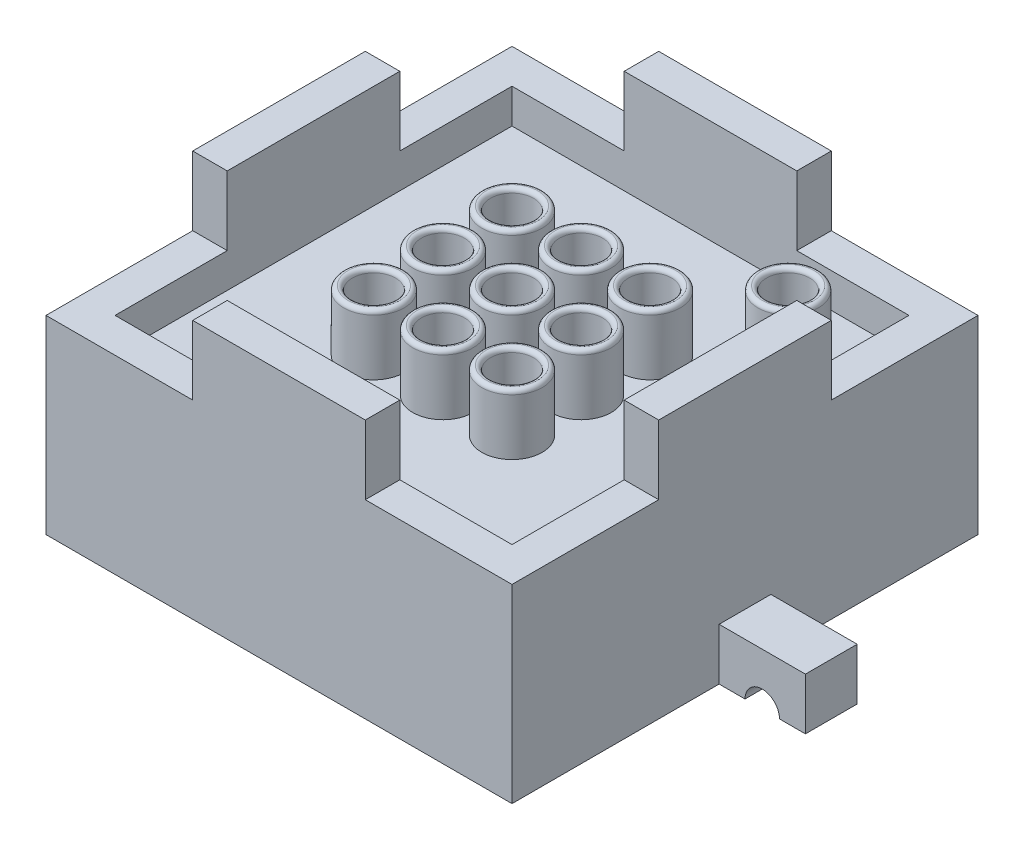
SolidWorks part; units mm, degrees
ref_plane "Front Plane" through (0, 0, 0) normal (0, 0, 1) x (1, 0, 0)
ref_plane "Top Plane" through (0, 0, 0) normal (0, 1, 0) x (1, 0, 0)
ref_plane "Right Plane" through (0, 0, 0) normal (1, 0, 0) x (0, 0, -1)
sketch "Sketch1" plane through (0, 0, 0) normal (0, 1, 0) x (1, 0, 0)
  line L0 (-13.5, 13.5) -> (13.5, 13.5)
  line L1 (-11.5, -11.5) -> (11.5, -11.5)
  line L2 (-11.5, -11.5) -> (-11.5, 11.5)
  line L3 (-11.5, 11.5) -> (11.5, 11.5)
  line L4 (11.5, -11.5) -> (11.5, 11.5)
  line L5 (-11.5, -11.5) -> (11.5, 11.5) construction
  line L6 (-11.5, 11.5) -> (11.5, -11.5) construction
  line L7 (13.5, -13.5) -> (13.5, 13.5)
  line L8 (-13.5, -13.5) -> (13.5, -13.5)
  line L9 (-13.5, -13.5) -> (-13.5, 13.5)
  point P0 (0, 0)
  dimension "D1" = 23
  dimension "D2" = 2
extrude "Boss-Extrude1" add sketch "Sketch1" along normal blind 2
sketch "Sketch2" plane through (0, 0, 0) normal (0, -1, 0) x (1, 0, 0)
  line L1 (-13.5, 13.5) -> (13.5, 13.5)
  line L2 (-13.5, 13.5) -> (-13.5, -13.5)
  line L3 (-13.5, -13.5) -> (13.5, -13.5)
  line L4 (13.5, 13.5) -> (13.5, -13.5)
  line L5 (-13.5, 13.5) -> (13.5, -13.5) construction
  line L6 (-13.5, -13.5) -> (13.5, 13.5) construction
  point P0 (0, 0)
extrude "Boss-Extrude2" add sketch "Sketch2" along normal blind 2
sketch "Sketch3" plane through (0, -2, 0) normal (0, -1, 0) x (1, 0, 0)
  line L0 (-11.5, 11.5) -> (11.5, 11.5)
  line L1 (-13.5, -13.5) -> (13.5, -13.5)
  line L2 (-13.5, -13.5) -> (-13.5, 13.5)
  line L3 (-13.5, 13.5) -> (13.5, 13.5)
  line L4 (13.5, -13.5) -> (13.5, 13.5)
  line L5 (-13.5, -13.5) -> (13.5, 13.5) construction
  line L6 (-13.5, 13.5) -> (13.5, -13.5) construction
  line L7 (11.5, -11.5) -> (11.5, 11.5)
  line L8 (-11.5, -11.5) -> (11.5, -11.5)
  line L9 (-11.5, -11.5) -> (-11.5, 11.5)
  point P0 (0, 0)
  dimension "D1" = 2
extrude "Boss-Extrude3" add sketch "Sketch3" along normal blind 5
sketch "Sketch6" plane through (0, 0, 0) normal (0, 1, 0) x (1, 0, 0)
  line L0 (11.5, -11.5) -> (11.5, 11.5) construction
  line L1 (11.5, 11.5) -> (-11.5, 11.5) construction
  circle A0 centre (8, 8) radius 1.75
  dimension "D2" = 3.5
  dimension "D1" = 3.5
  dimension "D3" = 3.5
extrude "Boss-Extrude5" add sketch "Sketch6" along normal blind 3.5
sketch "Sketch7" plane through (0, 3.5, 0) normal (0, 1, 0) x (1, 0, 0)
  circle A0 centre (8, 8) radius 1.25
  circle A1 centre (8, 8) radius 1.75 construction
  dimension "D1" = 0.5
extrude "Cut-Extrude2" cut sketch "Sketch7" against normal up to next
fillet "Fillet1" radius 0.25 2 edges at (8, 3.5, -6.25) (8, 3.5, -6.75)
pattern_linear "LPattern3" count 5 spacing 4 along (0, 0, 1) count 5 spacing 4 along (-1, 0, 0) skipping (0, 1), (0, 2), (0, 3), (0, 4), (1, 0), (1, 4), (2, 0), (2, 4), (3, 0), (3, 4), (4, 0), (4, 1), (4, 2), (4, 3), (4, 4) of "Boss-Extrude5", "Cut-Extrude2", "Fillet1"
sketch "Sketch11" plane through (0, -2, 0) normal (0, -1, 0) x (1, 0, 0)
  line L0 (11.5, 11.5) -> (-11.5, 11.5) construction
  line L1 (-11.5, 11.5) -> (-11.5, -11.5) construction
  circle A0 centre (-9.9, 9.9) radius 0.75
  dimension "D1" = 1.5
  dimension "D3" = 1.6
  dimension "D2" = 1.6
extrude "Boss-Extrude8" add sketch "Sketch11" along normal up to surface (5 mm away) up to face at (0, -7, 0)
pattern_linear "LPattern2" count 6 spacing 4 along (1, 0, 0) count 6 spacing 4 along (0, 0, -1) of "Boss-Extrude8"
sketch "Sketch8" plane through (0, -7, 0) normal (0, -1, 0) x (1, 0, 0)
  line L1 (-13.5, -13.5) -> (13.5, -13.5)
  line L2 (-13.5, -13.5) -> (-13.5, 13.5)
  line L3 (-13.5, 13.5) -> (13.5, 13.5)
  line L4 (13.5, -13.5) -> (13.5, 13.5)
  line L5 (-13.5, -13.5) -> (13.5, 13.5) construction
  line L6 (-13.5, 13.5) -> (13.5, -13.5) construction
  point P0 (0, 0)
extrude "Boss-Extrude6" add sketch "Sketch8" along normal blind 2
sketch "Sketch9" plane through (0, -9, 0) normal (0, -1, 0) x (1, 0, 0)
  circle A0 centre (0, 0) radius 4.25
  dimension "D1" = 8.5
extrude "Cut-Extrude3" cut sketch "Sketch9" against normal blind 7
sketch "Sketch10" plane through (0, 2, 0) normal (0, 1, 0) x (1, 0, 0)
  line L0 (-13.5, 0) -> (-11.5, 0) construction
  line L1 (-13.5, 13.5) -> (-13.5, -13.5) construction
  line L2 (-11.5, 11.5) -> (-11.5, -11.5) construction
  line L4 (-11.5, 5) -> (-13.5, 5)
  line L5 (-11.5, 5) -> (-11.5, -5)
  line L6 (-11.5, -5) -> (-13.5, -5)
  line L7 (-13.5, 5) -> (-13.5, -5)
  line L8 (-11.5, 5) -> (-13.5, -5) construction
  line L9 (-11.5, -5) -> (-13.5, 5) construction
  point P6 (-12.5, 0)
  dimension "D1" = 10
extrude "Boss-Extrude7" add sketch "Sketch10" along normal blind 4
pattern_circular "CirPattern2" count 4 over 360 about axis through (0, -7.001, 0) along (0, 1, 0) of "Boss-Extrude7"
sketch "Sketch12" plane through (-13.5, 0, 0) normal (-1, 0, 0) x (0, 0, 1)
  line L0 (13.5, -9) -> (-13.5, -9) construction
  line L1 (1.5, -6) -> (-1.5, -6)
  line L2 (1.5, -6) -> (1.5, -9)
  line L3 (1.5, -9) -> (-1.5, -9)
  line L4 (-1.5, -6) -> (-1.5, -9)
  line L5 (1.5, -6) -> (-1.5, -9) construction
  line L6 (1.5, -9) -> (-1.5, -6) construction
  line L7 (0, 0) -> (0, -9) construction
  point P0 (0, -7.5)
  dimension "D1" = 3
extrude "Boss-Extrude9" add sketch "Sketch12" along normal blind 5
pattern_circular "CirPattern1" count 2 over 360 about axis through (0, -7.001, 0) along (0, 1, 0) of "Boss-Extrude9"
sketch "Sketch13" plane through (0, 0, 1.5) normal (0, 0, 1) x (1, 0, 0)
  line L0 (18.5, -9) -> (13.5, -9) construction
  line L1 (15, -9) -> (17, -9)
  line L2 (-18.5, -9) -> (-13.5, -9) construction
  line L3 (-17, -9) -> (-15, -9)
  arc A0 (17, -9) -> (15, -9) centre (16, -9) ccw
  arc A1 (-15, -9) -> (-17, -9) centre (-16, -9) ccw
  dimension "D1" = 1
  dimension "D2" = 1
extrude "Cut-Extrude4" cut sketch "Sketch13" against normal up to next
equation "\"D3@Sketch6\"=\"D1@Sketch6\""
equation "\"D3@Sketch11\"=\"D2@Sketch11\""
equation "\"D2@Sketch13\"=\"D1@Sketch13\""
